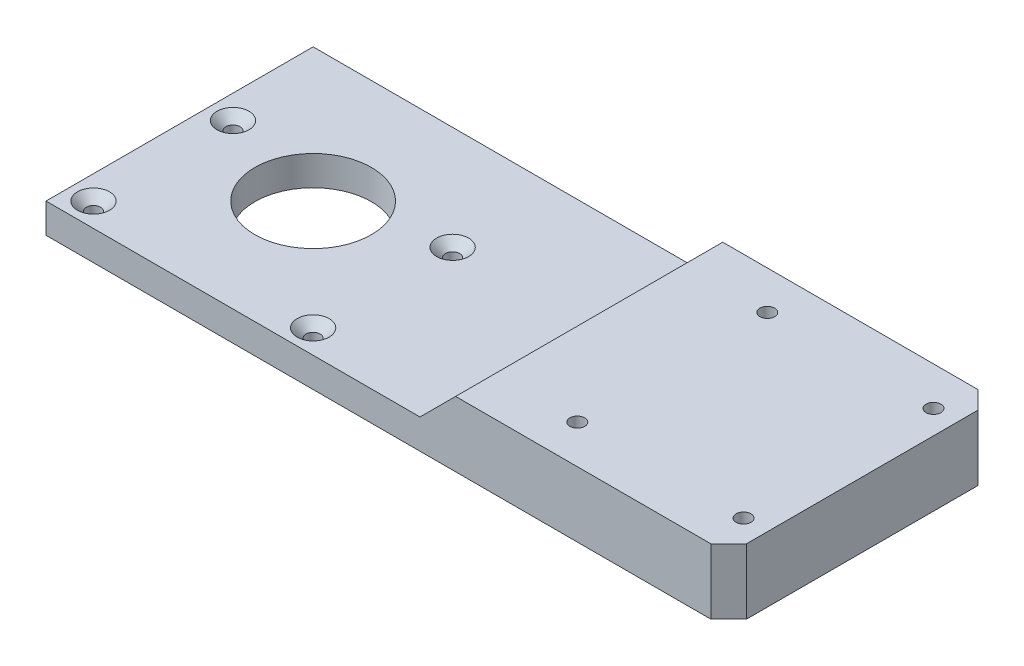
SolidWorks part; units mm, degrees
material "7075-T6, Plate (SS)"
ref_plane "Front Plane" through (0, 0, 0) normal (0, 0, 1) x (1, 0, 0)
ref_plane "Top Plane" through (0, 0, 0) normal (0, 1, 0) x (1, 0, 0)
ref_plane "Right Plane" through (0, 0, 0) normal (1, 0, 0) x (0, 0, -1)
sketch "Sketch1" plane through (0, 0, 0) normal (0, 1, 0) x (1, 0, 0)
  line L1 (0, -22.5) -> (115, -22.5)
  line L2 (0, -22.5) -> (0, 22.5)
  line L3 (0, 22.5) -> (115, 22.5)
  line L4 (115, -22.5) -> (115, 22.5)
  dimension "D1" = 45
  dimension "D2" = 115
extrude "Boss-Extrude1" add sketch "Sketch1" along normal blind 5 contours L2 L3 L4 L1
sketch "Sketch2" plane through (0, 5, 0) normal (0, 1, 0) x (1, 0, 0)
  line L0 (0, -22.5) -> (0, 22.5) construction
  circle A0 centre (22.5, 0) radius 9.8171
  dimension "D2" = 19.6342
  dimension "D1" = 22.5
extrude "Cut-Extrude1" cut sketch "Sketch2" against normal up to next
cosmetic thread "Cosmetic Thread1" parameters "D2"=20.32
hole_wizard "CSK for M2 Countersunk Flat Head Screw1" positions "Sketch3" profile "Sketch4" countersink size "M2" standard "DIN" end condition through all
sketch "Sketch3" plane through (0, 5, 0) normal (0, 1, 0) x (1, 0, 0)
  line L2 (0, -22.5) -> (115, -22.5) construction
  point P6 (4, -18.5)
  point P48 (41, -18.5)
  point P50 (41, 5)
  point P52 (4, 5)
  dimension "D3" = 4
  dimension "D5" = 37
  dimension "D6" = 27.5
sketch "Sketch4" plane through (4, 5, 18.5) normal (1, 0, 0) x (0, 0, 1)
  line L0 (0, 0) -> (0, 5)
  line L1 (0, 5) -> (1.2, 5)
  line L2 (1.2, 5) -> (1.2, 1.5)
  line L3 (1.2, 1.5) -> (2.7, 0)
  line L5 (2.7, 0) -> (0, 0)
  line L6 (-1.2, 1.5) -> (-2.7, 0) construction
  line L11 (0, -6.35) -> (0, 107.95) construction
  dimension "Thru Hole Dia." = 2.4
  dimension "Thru Hole Depth" = 5
  dimension "Near C'Sink Dia." = 5.4
  dimension "Near C'Sink Angle" = 90
sketch "Sketch13" plane through (0, 5, 0) normal (0, 1, 0) x (1, 0, 0)
  line L0 (0, -22.5) -> (115, -22.5) construction
  line L1 (115, 22.5) -> (63, 22.5)
  line L2 (115, 22.5) -> (115, -22.5)
  line L3 (115, -22.5) -> (63, -22.5)
  line L4 (63, 22.5) -> (63, -22.5)
  dimension "D1" = 52
extrude "Boss-Extrude4" add sketch "Sketch13" along normal blind 6
chamfer "Chamfer2" distance 6 angle 45 1 edges at (63, 11, 0)
hole_wizard "M3 Tapped Hole1" positions "Sketch5" profile "Sketch6" tap size "M3" standard "DIN" end condition through all
sketch "Sketch5" plane through (0, 11, 0) normal (0, 1, 0) x (1, 0, 0)
  line L1 (83, 16) -> (111, 16) construction
  line L2 (83, 16) -> (83, -16) construction
  line L3 (83, -16) -> (111, -16) construction
  line L4 (111, 16) -> (111, -16) construction
  circle A0 centre (22.5, 0) radius 9.8171 construction
  point P0 (83, 16)
  point P2 (111, 16)
  point P4 (83, -16)
  point P6 (111, -16)
  point P74 (83, 0)
  point P76 (97, 16)
  dimension "D1" = 74.5
  dimension "D2" = 28
  dimension "D3" = 32
sketch "Sketch6" plane through (83, 11, -16) normal (1, 0, 0) x (0, 0, 1)
  line L0 (0, 0) -> (0, 11)
  line L1 (0, 11) -> (1.25, 11)
  line L2 (1.25, 11) -> (1.25, 0)
  line L5 (1.25, 0) -> (0, 0)
  line L11 (0, -6.35) -> (0, 107.95) construction
  dimension "Thru Tap Drill Dia." = 2.5
  dimension "Thru Tap Drill Depth" = 11
cosmetic thread "Hole Thread7"
cosmetic thread "Hole Thread8"
cosmetic thread "Hole Thread9"
cosmetic thread "Hole Thread10"
chamfer "Chamfer1" distance 3 angle 45 2 edges at (115, 5.5, -22.5) (115, 5.5, 22.5)
